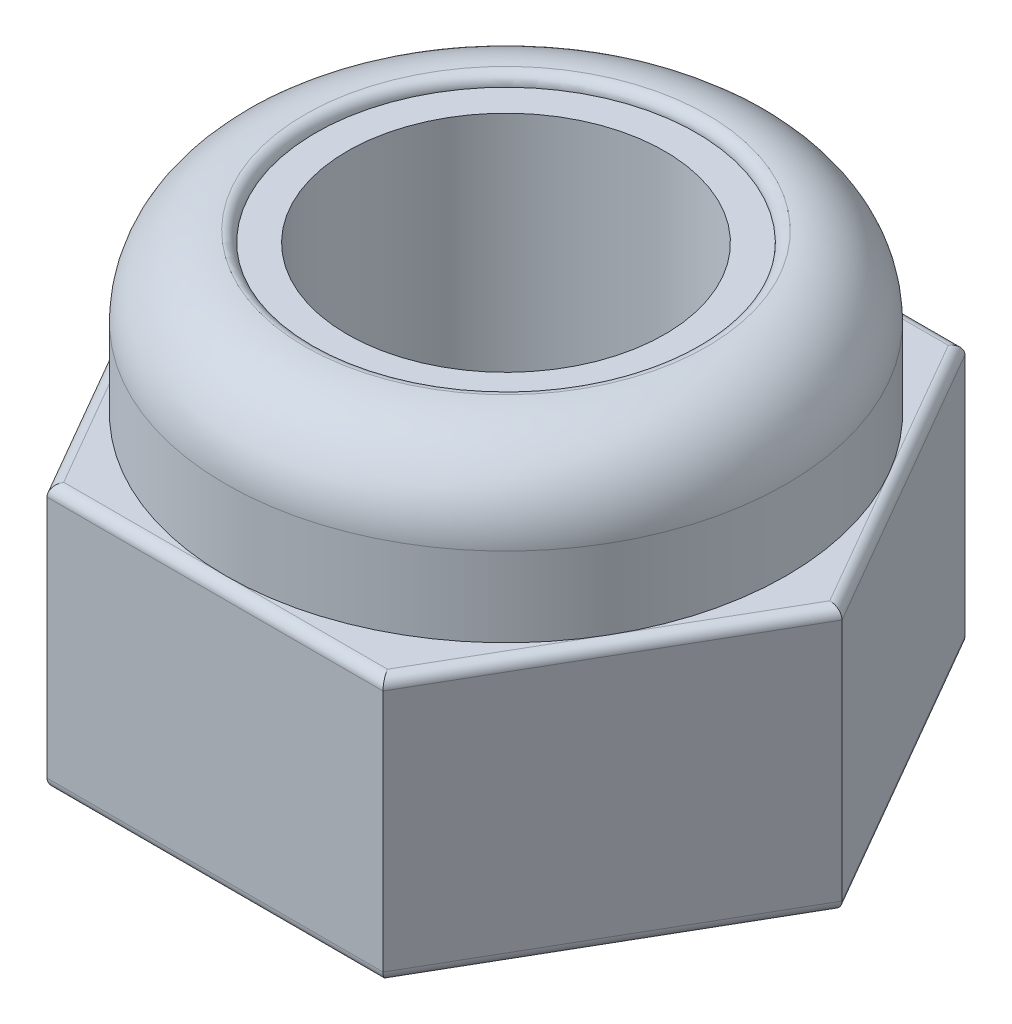
SolidWorks part; units mm, degrees
ref_plane "Front Plane" through (0, 0, 0) normal (0, 0, 1) x (1, 0, 0)
ref_plane "Top Plane" through (0, 0, 0) normal (0, 1, 0) x (1, 0, 0)
ref_plane "Right Plane" through (0, 0, 0) normal (1, 0, 0) x (0, 0, -1)
sketch "Sketch1" plane through (0, 0, 0) normal (0, 1, 0) x (1, 0, 0)
  line L1 (1.5877, -2.75) -> (3.1754, 0)
  line L2 (3.1754, 0) -> (1.5877, 2.75)
  line L3 (1.5877, 2.75) -> (-1.5877, 2.75)
  line L4 (-1.5877, 2.75) -> (-3.1754, 0)
  line L5 (-3.1754, 0) -> (-1.5877, -2.75)
  line L6 (-1.5877, -2.75) -> (1.5877, -2.75)
  circle A0 centre (0, 0) radius 2.75 construction
  circle A1 centre (0, 0) radius 1.5
  dimension "D1" = 3
  dimension "D2" = 5.5
extrude "Boss-Extrude1" add sketch "Sketch1" along normal blind 4
sketch "Sketch2" plane through (0, 0, 0) normal (1, 0, 0) x (0, 0, -1)
  line L0 (0, 4) -> (-2.75, 4) construction
  line L1 (-2.65, 3.25) -> (-2.65, 2.5)
  line L2 (-2.75, 4) -> (-2.75, 0) construction
  line L3 (-2.65, 2.5) -> (-5.25, 2.5)
  line L4 (-5.25, 2.5) -> (-5.25, 4)
  line L5 (-1.9, 4) -> (-1.9, 4.1)
  line L6 (0, 0) -> (-2.75, 0) construction
  line L7 (0, 4) -> (0, 0) construction
  line L8 (-1.9, 4.1) -> (-5.25, 4.1)
  line L9 (-5.25, 4.1) -> (-5.25, 4)
  arc A0 (-1.9, 4) -> (-2.65, 3.25) centre (-1.9, 3.25) ccw
  dimension "D1" = 0.75
  dimension "D2" = 0.1
  dimension "D3" = 2.5
  dimension "D4" = 0.1
  dimension "D5" = 2.5
revolve "Cut-Revolve3" cut sketch "Sketch2" angle 360 about L7
fillet "Fillet1" radius 0.1 13 edges at (0, 0, 1.5) (2.3816, 0, 1.375) (2.3816, 0, -1.375) (0, 0, -2.75) (-2.3816, 0, -1.375) (-2.3816, 0, 1.375) (0, 0, 2.75) (0, 2.5, -2.75) (2.3816, 2.5, 1.375) (0, 2.5, 2.75) (2.3816, 2.5, -1.375) (-2.3816, 2.5, -1.375) (-2.3816, 2.5, 1.375)
sketch "Sketch3" plane through (0, 4, 0) normal (0, 1, 0) x (1, 0, 0)
  circle A0 centre (0, 0) radius 1.8
  circle A1 centre (0, 0) radius 1.5
  circle A2 centre (0, 0) radius 1.5 construction
  dimension "D1" = 0.3
extrude "Cut-Extrude1" cut sketch "Sketch3" against normal blind 0.1
fillet "Fillet2" radius 0.1 1 edges at (0, 4, 1.8)
